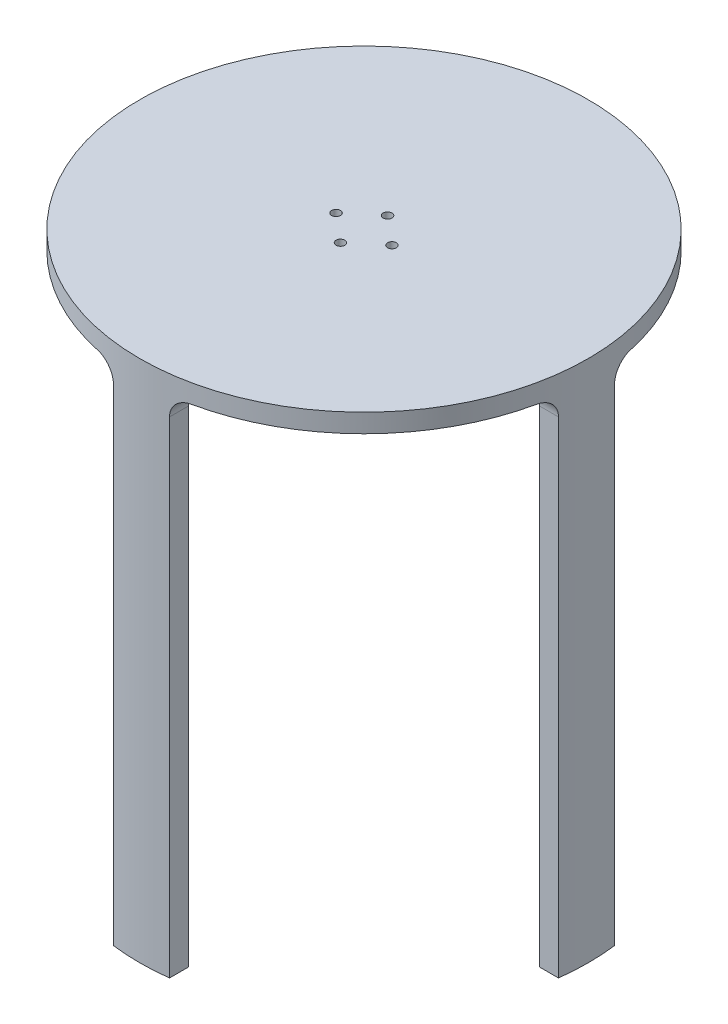
SolidWorks part; units mm, degrees
ref_plane "Front Plane" through (0, 0, 0) normal (0, 0, 1) x (1, 0, 0)
ref_plane "Top Plane" through (0, 0, 0) normal (0, 1, 0) x (1, 0, 0)
ref_plane "Right Plane" through (0, 0, 0) normal (1, 0, 0) x (0, 0, -1)
sketch "Sketch1" plane through (0, 0, 0) normal (0, 1, 0) x (1, 0, 0)
  line L1 (-76.2, -9.525) -> (76.2, -9.525)
  line L2 (-76.2, -9.525) -> (-76.2, 9.525)
  line L3 (-76.2, 9.525) -> (76.2, 9.525)
  line L4 (76.2, -9.525) -> (76.2, 9.525)
  line L5 (-76.2, -9.525) -> (76.2, 9.525) construction
  line L6 (-76.2, 9.525) -> (76.2, -9.525) construction
  line L7 (-9.525, -76.2) -> (9.525, -76.2)
  line L8 (-9.525, -76.2) -> (-9.525, 76.2)
  line L9 (-9.525, 76.2) -> (9.525, 76.2)
  line L10 (9.525, -76.2) -> (9.525, 76.2)
  line L11 (-9.525, -76.2) -> (9.525, 76.2) construction
  line L12 (-9.525, 76.2) -> (9.525, -76.2) construction
  circle A0 centre (0, 0) radius 76.2
  circle A1 centre (0, 0) radius 69.85
  point P13 (0, 0)
  dimension "D1" = 152.4
  dimension "D3" = 19.05
  dimension "D4" = 152.4
  dimension "D2" = 6.35
extrude "Boss-Extrude1" add sketch "Sketch1" along normal blind 171.45 contours A1 L3 A0 L1 | A1 L10 A0 L8 | A1 L1 A0 L3 | A1 L8 A0 L10 region at (-72.8165, 0, 0) region at (0, 0, 72.8165) region at (0, 0, -72.8165) region at (72.8165, 0, 0)
sketch "Sketch2" plane through (0, 171.45, 0) normal (0, 1, 0) x (1, 0, 0)
  circle A0 centre (0, 0) radius 76.2
extrude "Boss-Extrude2" add sketch "Sketch2" along normal blind 6.35
sketch "Sketch3" plane through (0, 177.8, 0) normal (0, 1, 0) x (1, 0, 0)
  line L0 (-9.5, 0) -> (9.5, 0) construction
  line L1 (0, -8) -> (0, 8) construction
  circle A0 centre (0, 8) radius 1.5
  circle A1 centre (9.5, 0) radius 1.5
  circle A2 centre (0, -8) radius 1.5
  circle A3 centre (-9.5, 0) radius 1.5
  point P5 (0, 0)
  point P9 (0, 0)
  dimension "D3" = 3
  dimension "D1" = 19
  dimension "D2" = 16
extrude "Cut-Extrude1" cut sketch "Sketch3" against normal blind 6.35
fillet "Fillet1" radius 6.35 12 edges at (72.3999, 171.45, -9.525) (72.3999, 171.45, 9.525) (69.85, 171.45, 0) (-9.525, 171.45, -72.3999) (9.525, 171.45, -72.3999) (0, 171.45, -69.85) (-72.3999, 171.45, -9.525) (-69.85, 171.45, 0) (-72.3999, 171.45, 9.525) (0, 171.45, 69.85) (-9.525, 171.45, 72.3999) (9.525, 171.45, 72.3999)
